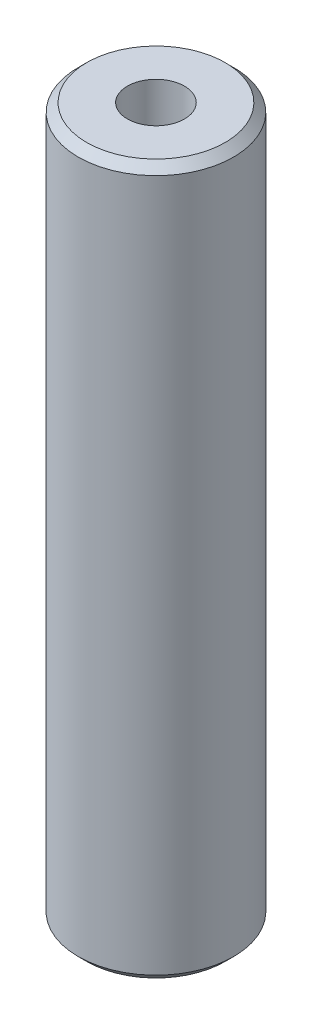
SolidWorks part; units mm, degrees
ref_plane "Front Plane" through (0, 0, 0) normal (0, 0, 1) x (1, 0, 0)
ref_plane "Top Plane" through (0, 0, 0) normal (0, 1, 0) x (1, 0, 0)
ref_plane "Right Plane" through (0, 0, 0) normal (1, 0, 0) x (0, 0, -1)
sketch "Sketch1" plane through (0, 0, 0) normal (0, 1, 0) x (1, 0, 0)
  circle A0 centre (0, 0) radius 52.5
  dimension "SHAFT_OD" = 105
extrude "Boss-Extrude1" add sketch "Sketch1" along normal blind 479.3587
sketch "Sketch2" plane through (0, 0, 0) normal (0, 1, 0) x (1, 0, 0)
  circle A0 centre (0, 0) radius 19.2746
  dimension "BORE_D" = 38.5491
extrude "Cut-Extrude1" cut sketch "Sketch2" along normal through all
chamfer "Chamfer1" distance 5.6942 angle 45 2 edges at (0, 479.3587, 52.5) (0, 0, 52.5)
